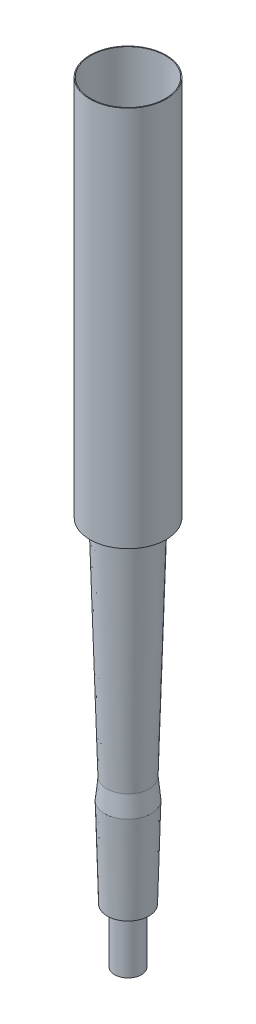
SolidWorks part; units mm, degrees
ref_plane "Front Plane" through (0, 0, 0) normal (0, 0, 1) x (1, 0, 0)
ref_plane "Top Plane" through (0, 0, 0) normal (0, 1, 0) x (1, 0, 0)
ref_plane "Right Plane" through (0, 0, 0) normal (1, 0, 0) x (0, 0, -1)
sketch "Sketch1" plane through (0, 0, 0) normal (0, 1, 0) x (1, 0, 0)
  circle A0 centre (0, 0) radius 1.67
  circle A1 centre (0, 0) radius 1.5
  dimension "D1" = 3.34
  dimension "D2" = 3
extrude "Boss-Extrude1" add sketch "Sketch1" along normal blind 6.8 contours A1 | A0
ref_plane "Plane2" through (0, 0, 0) normal (0, 0, 1) x (1, 0, 0)
sketch "Sketch4" plane through (0, 0, 0) normal (0, 0, 1) x (1, 0, 0)
  line L0 (0, 6.8) -> (2.6, 6.8)
  line L1 (1.5, 6.8) -> (-1.5, 6.8) construction
  line L2 (0, 6.8) -> (0, 18)
  line L3 (0, 18) -> (2.9, 18)
  line L4 (2.9, 18) -> (2.6, 6.8)
  dimension "D1" = 2.6
  dimension "D2" = 11.2
  dimension "D3" = 2.9
revolve "Revolve3" add sketch "Sketch4" angle 360 about L2
shell "Shell1" thickness 0.1 removed face at (2.9, 18, 0)
sketch "Sketch5" plane through (0, 0, 0) normal (0, 0, 1) x (1, 0, 0)
  line L0 (0, 18) -> (0, 20.5)
  line L1 (2.9, 18) -> (-2.9, 18) construction
  line L2 (-2.65, 20.5) -> (2.65, 20.5)
  line L3 (-2.65, 20.5) -> (-2.9, 18)
  line L4 (0, 20.5) -> (0, 48.5)
  line L5 (-3.45, 48.5) -> (-4.75, 48.5)
  line L6 (-3.45, 48.5) -> (-2.65, 20.5)
  line L7 (-4.75, 48.5) -> (-4.75, 96.04)
  line L8 (0, 0) -> (0, 96.04)
  line L9 (0, 96.04) -> (-4.75, 96.04)
  line L10 (0, 18) -> (-2.9, 18)
  point P8 (0, 20.5)
  point P13 (0, 48.5)
  point P16 (0, 48.5)
  dimension "D1" = 2.5
  dimension "D2" = 5.3
  dimension "D3" = 28
  dimension "D5" = 96.04
revolve "Revolve5" add sketch "Sketch5" angle 360 about L8 region at (-2.1442, 62.0735, 0)
shell "Shell3" thickness 0.1 removed face at (0, 96.04, -4.75)
sketch "Sketch6" plane through (0, 0, 0) normal (0, 0, 1) x (1, 0, 0)
  line L0 (0, 18.1048) -> (0, 20.5664)
  line L1 (0, 18.1048) -> (2.9, 18)
  line L2 (2.9, 18) -> (2.65, 20.5664)
  line L3 (2.65, 20.5664) -> (0, 20.5664)
revolve "Revolve6" add sketch "Sketch6" angle 360 about L0
sketch "Sketch7" plane through (0, 0, 0) normal (0, 1, 0) x (1, 0, 0)
  circle A0 centre (0, 0) radius 1.5
extrude "Cut-Extrude2" cut sketch "Sketch7" along normal blind 10080 and the other way through all
